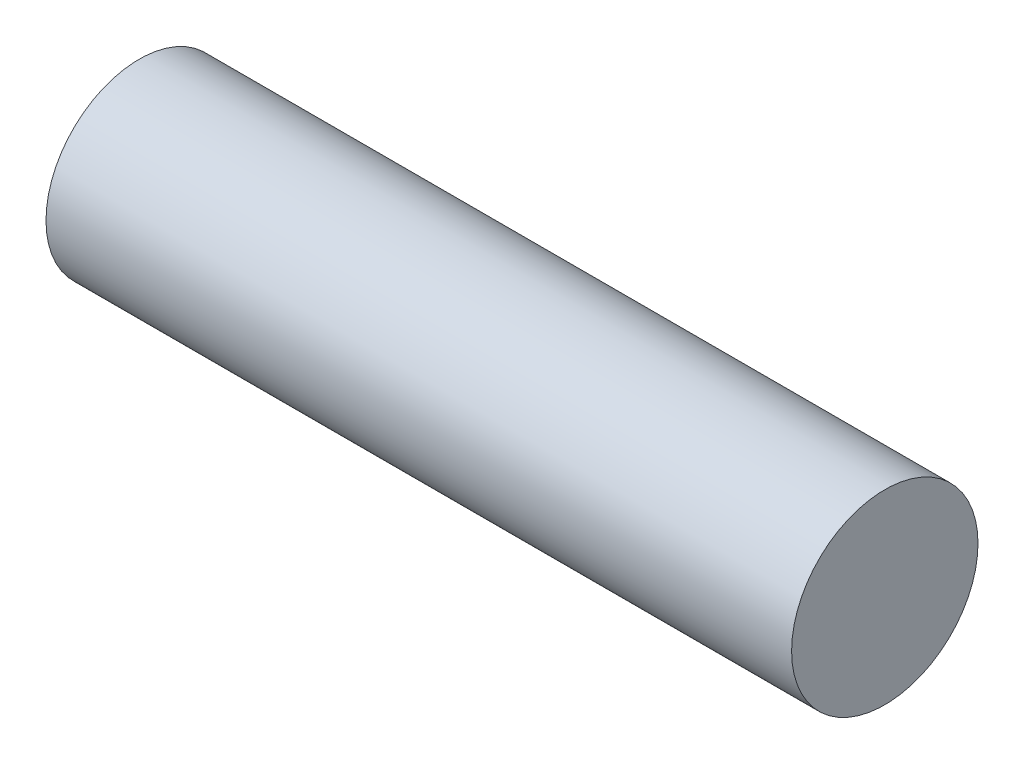
SolidWorks part; units mm, degrees
ref_plane "Front Plane" through (0, 0, 0) normal (0, 0, 1) x (1, 0, 0)
ref_plane "Top Plane" through (0, 0, 0) normal (0, 1, 0) x (1, 0, 0)
ref_plane "Right Plane" through (0, 0, 0) normal (1, 0, 0) x (0, 0, -1)
sketch "Sketch1" plane through (0, 0, 0) normal (1, 0, 0) x (0, 0, -1)
  circle A0 centre (0, 0) radius 1
  dimension "D1" = 2
extrude "Boss-Extrude1" add sketch "Sketch1" along normal blind 4 and the other way blind 4
